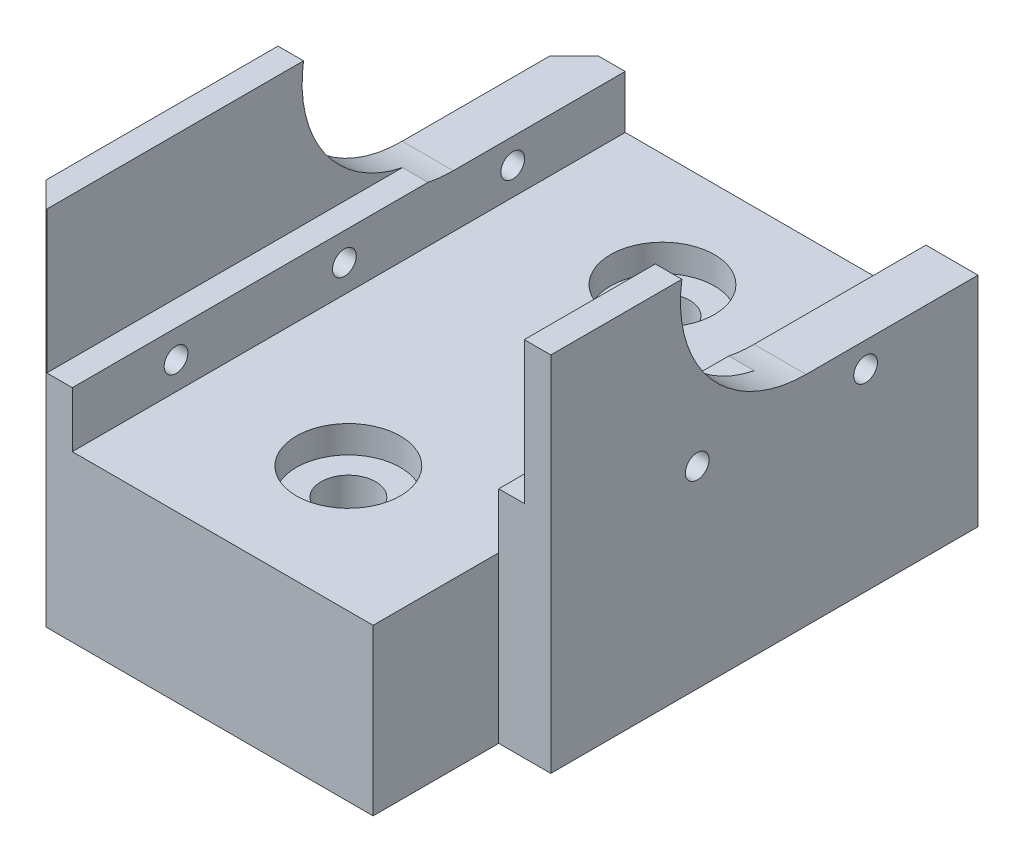
SolidWorks part; units mm, degrees
material "PLA"
ref_plane "Front Plane" through (0, 0, 0) normal (0, 0, 1) x (1, 0, 0)
ref_plane "Top Plane" through (0, 0, 0) normal (0, 1, 0) x (1, 0, 0)
ref_plane "Right Plane" through (0, 0, 0) normal (1, 0, 0) x (0, 0, -1)
sketch "Sketch1" plane through (0, 0, 0) normal (0, 1, 0) x (1, 0, 0)
  line L0 (-22.86, 30.48) -> (22.86, 30.48)
  line L6 (-22.86, 30.48) -> (-22.86, -30.48)
  line L8 (22.86, 30.48) -> (22.86, -30.48)
  line L9 (-22.86, -30.48) -> (22.86, -30.48)
  point P1 (-22.86, 0)
  point P7 (22.86, 0)
  dimension "D3" = 30.48
  dimension "D2" = 45.72
  dimension "D1" = 60.96
  dimension "D4" = 22.86
extrude "Boss-Extrude1" add sketch "Sketch1" along normal blind 6.35
sketch "Sketch2" plane through (0, 6.35, 0) normal (0, 1, 0) x (1, 0, 0)
  line L9 (-22.86, -30.48) -> (22.86, -30.48) construction
  line L10 (-22.86, 30.48) -> (-15.2, 30.48)
  line L11 (-22.86, 30.48) -> (-22.86, -30.48)
  line L12 (-22.86, -30.48) -> (-15.2, -30.48)
  line L13 (-15.2, 30.48) -> (-15.2, -30.48)
  line L14 (22.86, 30.48) -> (-22.86, 30.48) construction
  line L15 (15.2, 30.48) -> (22.86, 30.48)
  line L16 (15.2, 30.48) -> (15.2, -30.48)
  line L17 (15.2, -30.48) -> (22.86, -30.48)
  line L18 (22.86, 30.48) -> (22.86, -30.48)
  dimension "D1" = 7.66
  dimension "D2" = 7.66
extrude "Boss-Extrude2" add sketch "Sketch2" along normal blind 20.955
hole_wizard "M2 Clearance Hole2" positions "Sketch6" profile "Sketch7" hole size "M2" standard "ANSI Metric"
sketch "Sketch6" plane through (22.86, 0, 0) normal (1, 0, 0) x (0, 0, -1)
  line L0 (-30.48, 27.305) -> (-30.48, 0) construction
  line L1 (-30.48, 0) -> (30.48, 0) construction
  point P0 (-14.9172, 10.16)
  dimension "D1" = 15.5628
  dimension "D2" = 10.16
sketch "Sketch7" plane through (22.86, 10.16, 14.9172) normal (0, 1, 0) x (0, 0, -1)
  line L0 (0, 0) -> (0, 46.441)
  line L1 (0, 46.441) -> (1.2, 45.72)
  line L2 (1.2, 45.72) -> (1.2, 0)
  line L5 (1.2, 0) -> (0, 0)
  line L10 (0, 46.441) -> (-1.2, 45.72) construction
  line L11 (0, -6.35) -> (0, 107.95) construction
  dimension "Hole Dia." = 2.4
  dimension "Hole Depth" = 45.72
  dimension "Drill Angle" = 118
pattern_linear "LPattern1" count 3 spacing 17.018 along (0, 0, -1) of "M2 Clearance Hole2"
extrude "Boss-Extrude3" add sketch "Sketch1<3>" against normal blind 2.54
sketch "Sketch1<3>" plane through (0, 0, 0) normal (0, 1, 0) x (1, 0, 0) same geometry as "Sketch1"
sketch "Sketch8" plane through (-22.86, 0, 0) normal (-1, 0, 0) x (0, 0, 1)
  line L0 (-30.48, 27.305) -> (-30.48, -2.54) construction
  line L1 (-30.48, -2.54) -> (-14.605, -2.54)
  line L2 (-30.48, -2.54) -> (-30.48, 3.81)
  line L3 (-30.48, 3.81) -> (-14.605, 3.81)
  line L4 (-14.605, -2.54) -> (-14.605, 3.81)
  line L5 (-30.48, -2.54) -> (30.48, -2.54) construction
  dimension "D1" = 15.875
  dimension "D2" = 6.35
sketch "Sketch11" plane through (15.2, 0, 0) normal (-1, 0, 0) x (0, 0, 1)
  line L0 (30.48, 27.305) -> (30.48, 6.35) construction
  line L1 (-30.48, 27.305) -> (30.48, 27.305)
  line L2 (-30.48, 27.305) -> (-30.48, 12.96)
  line L3 (-30.48, 12.96) -> (30.48, 12.96)
  line L4 (30.48, 27.305) -> (30.48, 12.96)
  dimension "D1" = 14.345
extrude "Cut-Extrude1" cut sketch "Sketch11" against normal mid plane 35.56 from surface starting at plane "Right Plane"
sketch "Sketch12" plane through (22.86, 0, 0) normal (1, 0, 0) x (0, 0, -1)
  line L0 (30.48, 27.305) -> (30.48, -2.54) construction
  line L1 (13.105, 12.7) -> (30.48, 12.7)
  line L2 (30.48, 12.7) -> (30.48, 27.305)
  line L3 (30.48, 27.305) -> (25.6613, 27.305)
  line L5 (-30.48, 27.305) -> (30.48, 27.305) construction
  arc A0 (25.6613, 27.305) -> (13.105, 12.7) centre (13.105, 25.4) ccw
  dimension "D3" = 25.4
  dimension "D1" = 17.375
  dimension "D2" = 1.905
extrude "Cut-Extrude2" cut sketch "Sketch12" against normal through all
fillet "Fillet3" [suppressed] radius 0.762
sketch "Sketch17" plane through (0, -2.54, 0) normal (0, -1, 0) x (1, 0, 0)
  line L0 (-22.86, 30.48) -> (22.86, 30.48) construction
  line L1 (-22.86, 30.48) -> (22.86, 30.48)
  line L2 (-22.86, 30.48) -> (-22.86, -30.48)
  line L3 (-22.86, -30.48) -> (22.86, -30.48)
  line L4 (22.86, 30.48) -> (22.86, -30.48)
  line L5 (22.86, -30.48) -> (-22.86, -30.48) construction
  line L6 (22.86, 30.48) -> (22.86, -30.48) construction
  line L7 (-22.86, -30.48) -> (-22.86, 30.48) construction
extrude "Boss-Extrude4" add sketch "Sketch17" along normal blind 6.785
fillet "Fillet5" [suppressed] radius 0.762
sketch "Sketch19" plane through (0, 6.35, 0) normal (0, 1, 0) x (1, 0, 0)
  line L0 (15.2, 30.48) -> (15.2, -30.48) construction
  line L1 (-15.2, -30.48) -> (15.2, -30.48)
  line L2 (-15.2, -30.48) -> (-15.2, 30.48)
  line L3 (-15.2, 30.48) -> (15.2, 30.48)
  line L4 (15.2, -30.48) -> (15.2, 30.48)
  line L5 (15.2, 30.48) -> (-15.2, 30.48) construction
extrude "Boss-Extrude5" add sketch "Sketch19" along normal blind 1.01
hole_wizard "CBORE for M5 SBHCS2" positions "Sketch20" profile "Sketch21" counterbore size "M5" standard "ANSI Metric" end condition through all
sketch "Sketch20" plane through (0, 7.36, 0) normal (0, 1, 0) x (1, 0, 0)
  point P2 (0, -12.7)
  point P5 (0, 19.05)
  dimension "D1" = 31.75
  dimension "D2" = 12.7
sketch "Sketch21" plane through (0, 7.36, 12.7) normal (1, 0, 0) x (0, 0, 1)
  line L0 (0, 0) -> (0, 16.685)
  line L1 (0, 16.685) -> (2.75, 16.685)
  line L3 (2.75, 16.685) -> (2.75, 2.75)
  line L4 (2.75, 2.75) -> (5.25, 2.75)
  line L5 (5.25, 2.75) -> (5.25, 0)
  line L7 (5.25, 0) -> (0, 0)
  line L11 (0, -6.35) -> (0, 107.95) construction
  dimension "Thru Hole Dia." = 5.5
  dimension "Thru Hole Depth" = 16.685
  dimension "C'Bore Dia." = 10.5
  dimension "C'Bore Depth" = 2.75
fillet "Fillet6" [suppressed] radius 0.762
sketch "Sketch24" plane through (31.5712, -12.7, -14.6188) normal (0, 1, 0) x (0, 0, -1)
  line L0 (-45.0988, 8.7112) -> (-14.0701, 8.7112) construction
  line L1 (-45.0988, 54.4312) -> (-40.0188, 54.4312)
  line L2 (-45.0988, 54.4312) -> (-45.0988, 8.7112)
  line L3 (-45.0988, 8.7112) -> (-40.0188, 8.7112)
  line L4 (-40.0188, 54.4312) -> (-40.0188, 8.7112)
  dimension "D1" = 5.08
extrude "Cut-Extrude3" cut sketch "Sketch24" against normal through all both and the other way through all
sketch "Sketch25" plane through (0, 0, 25.4) normal (0, 0, 1) x (1, 0, 0)
  line L0 (15.2, -9.325) -> (15.2, 27.305)
  line L1 (22.86, -9.325) -> (-22.86, -9.325) construction
  line L3 (22.86, 27.305) -> (22.86, -9.325) construction
  line L4 (15.2, -9.325) -> (22.86, -9.325)
  line L5 (22.86, -9.325) -> (22.86, 27.305)
  line L6 (22.86, 27.305) -> (17.78, 27.305) construction
  line L7 (15.2, 27.305) -> (22.86, 27.305)
  line L8 (15.2, 12.96) -> (15.2, 7.36) construction
extrude "Cut-Extrude4" cut sketch "Sketch25" against normal blind 12.7
sketch "Sketch26" plane through (0, 0, 25.4) normal (0, 0, 1) x (1, 0, 0)
  line L0 (22.86, 27.305) -> (17.78, 27.305) construction
  line L1 (20.46, 27.305) -> (22.86, 27.305)
  line L2 (20.46, 27.305) -> (20.46, -9.325)
  line L3 (20.46, -9.325) -> (22.86, -9.325)
  line L4 (22.86, 27.305) -> (22.86, -9.325)
  line L5 (20.46, 27.305) -> (22.86, -9.325) construction
  line L6 (20.46, -9.325) -> (22.86, 27.305) construction
  line L8 (15.2, -9.325) -> (22.86, -9.325) construction
  line L9 (22.86, -9.325) -> (22.86, 27.305) construction
  point P0 (21.66, 8.99)
  dimension "D1" = 2.4
extrude "Cut-Extrude5" cut sketch "Sketch26" against normal through all
sketch "Sketch27" plane through (0, 0, 25.4) normal (0, 0, 1) x (1, 0, 0)
  line L0 (-17.78, 27.305) -> (-22.86, 27.305) construction
  line L1 (-22.86, 27.305) -> (-20.36, 27.305)
  line L2 (-22.86, 27.305) -> (-22.86, -9.325)
  line L3 (-22.86, -9.325) -> (-20.36, -9.325)
  line L4 (-20.36, 27.305) -> (-20.36, -9.325)
  line L5 (-22.86, 27.305) -> (-20.36, -9.325) construction
  line L6 (-22.86, -9.325) -> (-20.36, 27.305) construction
  line L7 (15.2, -9.325) -> (-22.86, -9.325) construction
  line L8 (-22.86, 27.305) -> (-22.86, -9.325) construction
  point P0 (-21.61, 8.99)
  dimension "D1" = 2.5
extrude "Cut-Extrude6" cut sketch "Sketch27" against normal through all
chamfer "Chamfer1" distance 2.5 angle 45 2 edges at (-20.36, 8.99, 25.4) (-20.36, 1.6875, -30.48)
